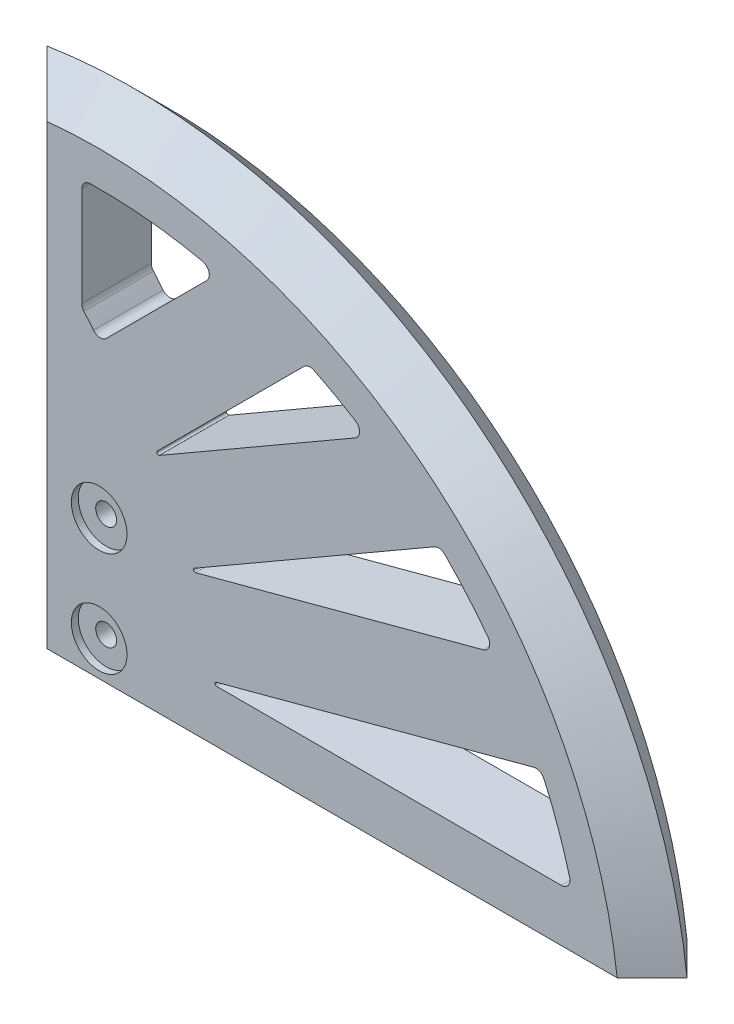
SolidWorks part; units mm, degrees
ref_plane "Front Plane" through (0, 0, 0) normal (0, 0, 1) x (1, 0, 0)
ref_plane "Top Plane" through (0, 0, 0) normal (0, 1, 0) x (1, 0, 0)
ref_plane "Right Plane" through (0, 0, 0) normal (1, 0, 0) x (0, 0, -1)
sketch "Sketch1" plane through (0, 0, 0) normal (0, 0, 1) x (1, 0, 0)
  line L0 (0, 0) -> (0, 27.8325)
  line L1 (0, 0) -> (37.7969, 0)
  line L3 (12, 3) -> (33.211, 3)
  line L6 (5, 18) -> (5, 24.3821)
  line L7 (12, 3) -> (31.3937, 8.1965)
  line L9 (10.8085, 7.8571) -> (28.7851, 12.6739)
  line L12 (10.8085, 7.8571) -> (25.5994, 16.3966)
  line L14 (8.8112, 12.4775) -> (21.4315, 19.7638)
  line L16 (8.8112, 12.4775) -> (18.0217, 21.6879)
  line L17 (12.8195, 23.5568) -> (6.0223, 16.7597)
  circle A2 centre (6, 2) radius 0.6
  circle A3 centre (6, 8) radius 0.6
  arc A17 (0, 27.8325) -> (37.7969, 0) centre (6, -3.6) cw
  arc A24 (5, 24.3821) -> (33.211, 3) centre (6, -3.6) cw
  arc A25 (5, 18) -> (12, 3) centre (-17.6305, -1.6942) cw
  point P36 (0, 0)
  dimension "D4" = 1.2
  dimension "D12" = 6
  dimension "D14" = 32
  dimension "D15" = 5
  dimension "D13" = 12
  dimension "D9" = 3
  dimension "D18" = 30
  dimension "D7" = 28
  dimension "D8" = 30
  dimension "D3" = 2
  dimension "D6" = 6
  dimension "D10" = 3.6
  dimension "D11" = 5
  dimension "D16" = 15
  dimension "D17" = 5
  dimension "D19" = 5
  dimension "D20" = 45
  dimension "20" = 18
  dimension "D5" = 2
extrude "Boss-Extrude1" add sketch "Sketch1" along normal blind 4 contours A17 L0 L1 A25 L6 A24 L3 A3 A2 | L9 A25 L7 A24 | L14 A25 L12 A24 | L6 A25 L16 A24 L17 region at (0.4728, 13.9162, 0) region at (20.8325, 7.9222, 0) region at (16.7737, 14.1119, 0) region at (11.5805, 18.6055, 0)
fillet "Fillet3" radius 0.1 3 edges at (8.8112, 12.4775, 2) (10.8085, 7.8571, 2) (12, 3, 2)
fillet "Fillet4" radius 0.5 10 edges at (33.211, 3, 2) (31.3937, 8.1965, 2) (28.7851, 12.6739, 2) (25.5994, 16.3966, 2) (21.4315, 19.7638, 2) (18.0217, 21.6879, 2) (12.8195, 23.5568, 2) (5, 24.3821, 2) (5, 18, 2) (6.0223, 16.7597, 2)
sketch "Sketch6" plane through (0, 0, 0) normal (0, -1, 0) x (1, 0, 0)
  line L0 (0, 2) -> (37.7969, 2) construction
  line L1 (0, 4) -> (0, 0) construction
  line L2 (37.7969, 4) -> (37.7969, 0) construction
  line L3 (6, 2.75) -> (6, 1.25) construction
  line L4 (8.75, 2.75) -> (3.25, 2.75)
  line L5 (8.75, 2.75) -> (8.75, 1.25)
  line L6 (8.75, 1.25) -> (3.25, 1.25)
  line L7 (3.25, 2.75) -> (3.25, 1.25)
  point P10 (8.75, 2)
  dimension "D1" = 1.5
  dimension "D2" = 6
  dimension "D3" = 5.5
extrude "Cut-Extrude3" cut sketch "Sketch6" against normal blind 12.5
chamfer "Chamfer5" distance 2 angle 45 1 edges at (24.9745, 22.1676, 0)
chamfer "Chamfer6" distance 2 angle 45 1 edges at (24.9745, 22.1676, 4)
chamfer "Chamfer7" distance 1 angle 45 1 edges at (0, 12.8969, 0)
chamfer "Chamfer8" distance 3 angle 45 1 edges at (0, 12.8969, 4)
sketch "Sketch8" plane through (0, 0, 4) normal (0, 0, 1) x (1, 0, 0)
  circle A2 centre (6, 8) radius 1.6
  circle A3 centre (6, 8) radius 1.6
  circle A5 centre (6, 2) radius 1.6
  circle A6 centre (6, 2) radius 1.6
  dimension "D1" = 1
  dimension "D2" = 1
extrude "Cut-Extrude4" cut sketch "Sketch8" against normal blind 0.4
extrude "Cut-Extrude5" cut sketch "Sketch8<2>" against normal blind 4 from offset 3.6 offset against normal yes
sketch "Sketch8<2>" plane through (0, 0, 4) normal (0, 0, 1) x (1, 0, 0) same geometry as "Sketch8"
fillet "Fillet5" radius 2 1 edges at (8.75, 12.5, 2)
